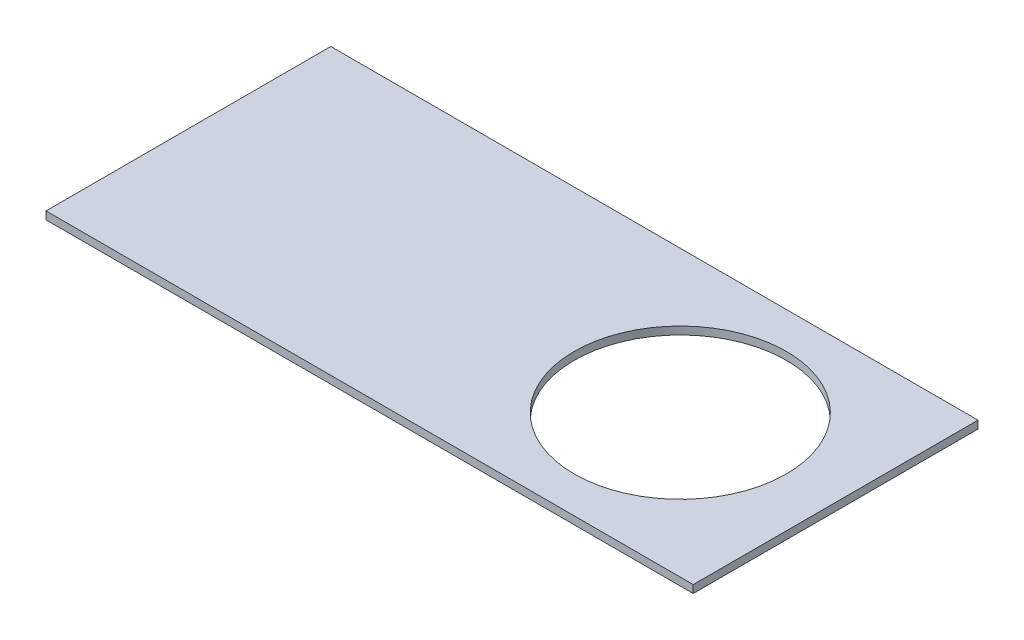
SolidWorks part; units mm, degrees
material "Сталь 3 ГОСТ 535-88"
ref_plane "Спереди" through (0, 0, 0) normal (0, 0, 1) x (1, 0, 0)
ref_plane "Сверху" through (0, 0, 0) normal (0, 1, 0) x (1, 0, 0)
ref_plane "Справа" through (0, 0, 0) normal (1, 0, 0) x (0, 0, -1)
sketch "Эскиз1" plane through (0, 0, 0) normal (0, 1, 0) x (1, 0, 0)
  line L1 (-125, -55) -> (125, -55)
  line L2 (-125, -55) -> (-125, 55)
  line L3 (-125, 55) -> (125, 55)
  line L4 (125, -55) -> (125, 55)
  line L5 (0, 55) -> (0, -55) construction
  line L6 (-125, 0) -> (125, 0) construction
  circle A0 centre (65, 0) radius 41
  point P0 (0, 0)
  dimension "D3" = 82
  dimension "D1" = 250
  dimension "D2" = 110
  dimension "D4" = 60
extrude "Бобышка-Вытянуть1" add sketch "Эскиз1" along normal blind 3
sketch "Эскиз2" [suppressed] plane through (0, 5, 0) normal (0, 1, 0) x (1, 0, 0)
  circle A9 centre (110, -45) radius 3 construction
  circle A12 centre (-110, -45) radius 3 construction
  circle A13 centre (15, -45) radius 3 construction
  circle A15 centre (110, -45) radius 3
  circle A18 centre (-110, -45) radius 3
  circle A19 centre (15, -45) radius 3
  circle A21 centre (15, 45) radius 3 construction
  circle A22 centre (110, 45) radius 3 construction
  circle A23 centre (-110, 45) radius 3
  circle A24 centre (15, 45) radius 3
  circle A25 centre (110, 45) radius 3
extrude "Вырез-Вытянуть1" [suppressed] cut sketch "Эскиз2" against normal through all
chamfer "Фаска1" [suppressed] distance 3 angle 45
sketch "Эскиз3" [suppressed] plane through (0, 5, 0) normal (0, 1, 0) x (1, 0, 0)
  line L0 (0, 55) -> (0, -55) construction
  line L1 (-129.7495, 75.1925) -> (0, 75.1925)
  line L2 (-129.7495, 75.1925) -> (-129.7495, -71.235)
  line L3 (-129.7495, -71.235) -> (0, -71.235)
  line L4 (0, 75.1925) -> (0, -71.235)
extrude "Вырез-Вытянуть2" [suppressed] cut sketch "Эскиз3" against normal through all
